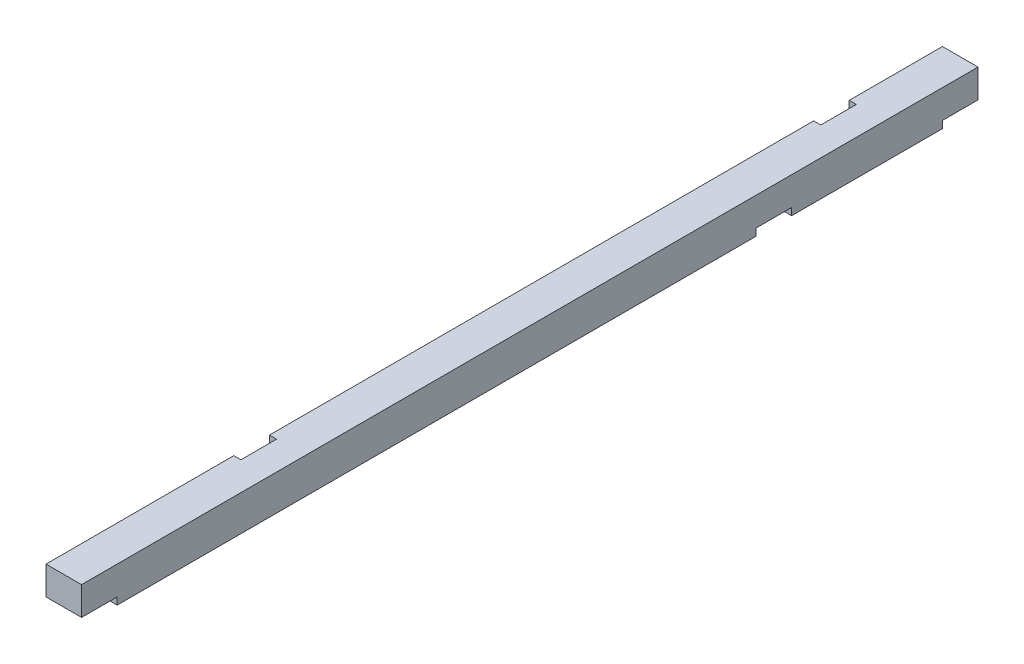
SolidWorks part; units mm, degrees
ref_plane "Plan de face" through (0, 0, 0) normal (0, 0, 1) x (1, 0, 0)
ref_plane "Plan de dessus" through (0, 0, 0) normal (0, 1, 0) x (1, 0, 0)
ref_plane "Plan de droite" through (0, 0, 0) normal (1, 0, 0) x (0, 0, -1)
sketch "Esquisse1" plane through (0, 0, 0) normal (0, 0, 1) x (1, 0, 0)
  line L0 (-5, 5) -> (5, -5) construction
  line L1 (-5, 5) -> (5, 5)
  line L2 (-5, 5) -> (-5, -5)
  line L3 (-5, -5) -> (5, -5)
  line L4 (5, 5) -> (5, -5)
  dimension "D1" = 10
extrude "Boss.-Extru.1" add sketch "Esquisse1" along normal blind 252
sketch "Esquisse2" plane through (-5, 0, 0) normal (-1, 0, 0) x (0, 0, 1)
  line L0 (0, -3) -> (0, -333) construction
  line L1 (0, -5) -> (10, -5)
  line L2 (0, -5) -> (0, -3)
  line L3 (0, -3) -> (10, -3)
  line L4 (10, -5) -> (10, -3)
  line L5 (10, -3) -> (10, -200) construction
  line L6 (52.4, -3) -> (52.4, -200) construction
  line L7 (52.4, -5) -> (62.4, -5)
  line L8 (52.4, -5) -> (52.4, -3)
  line L9 (52.4, -3) -> (62.4, -3)
  line L10 (62.4, -5) -> (62.4, -3)
  line L11 (62.4, -3) -> (62.4, -200) construction
  line L12 (242, -3) -> (242, -200) construction
  line L13 (242, -5) -> (252, -5)
  line L14 (242, -5) -> (242, -3)
  line L15 (242, -3) -> (252, -3)
  line L16 (252, -5) -> (252, -3)
  line L17 (252, -3) -> (252, -313) construction
  line L18 (252, -5) -> (0, -5) construction
  dimension "D1" = 2
extrude "Enlèv. mat.-Extru.1" cut sketch "Esquisse2" against normal through all
sketch "Esquisse3" plane through (0, -5, 0) normal (0, -1, 0) x (1, 0, 0)
  line L4 (3, 36.2) -> (3, 26.2)
  line L5 (224, 36.2) -> (3, 36.2)
  line L6 (224, 26.2) -> (224, 36.2)
  line L7 (3, 26.2) -> (224, 26.2)
  line L8 (3, 36.2) -> (3, 26.2)
  line L9 (224, 36.2) -> (3, 36.2)
  line L10 (224, 26.2) -> (224, 36.2)
  line L11 (3, 26.2) -> (224, 26.2)
  dimension "D1" = 0
extrude "Enlèv. mat.-Extru.2" [suppressed] cut sketch "Esquisse3" against normal through all
sketch "Esquisse4" plane through (0, 5, 0) normal (0, 1, 0) x (1, 0, 0)
  line L4 (3, -189.2) -> (3, -199.2)
  line L5 (3, -199.2) -> (224, -199.2)
  line L6 (224, -199.2) -> (224, -189.2)
  line L7 (224, -189.2) -> (3, -189.2)
  line L8 (3, -189.2) -> (3, -199.2)
  line L9 (3, -199.2) -> (224, -199.2)
  line L10 (224, -199.2) -> (224, -189.2)
  line L11 (224, -189.2) -> (3, -189.2)
  dimension "D1" = 0
extrude "Enlèv. mat.-Extru.3" [suppressed] cut sketch "Esquisse4" against normal through all
sketch "Esquisse5" plane through (0, 5, 0) normal (0, 1, 0) x (1, 0, 0)
  line L0 (3, -199.2) -> (224, -199.2) construction
  line L1 (-5, -199.2) -> (-3, -199.2)
  line L2 (-5, -199.2) -> (-5, -189.2)
  line L3 (-5, -189.2) -> (-3, -189.2)
  line L4 (-3, -199.2) -> (-3, -189.2)
  line L5 (3, -189.2) -> (224, -189.2) construction
  line L6 (3, -36.2) -> (224, -36.2) construction
  line L7 (-5, -36.2) -> (-3, -36.2)
  line L8 (-5, -36.2) -> (-5, -26.2)
  line L9 (-5, -26.2) -> (-3, -26.2)
  line L10 (-3, -36.2) -> (-3, -26.2)
  line L11 (3, -26.2) -> (224, -26.2) construction
  line L12 (-5, -252) -> (-5, 0) construction
  dimension "D1" = 2
extrude "Enlèv. mat.-Extru.4" cut sketch "Esquisse5" against normal through all
